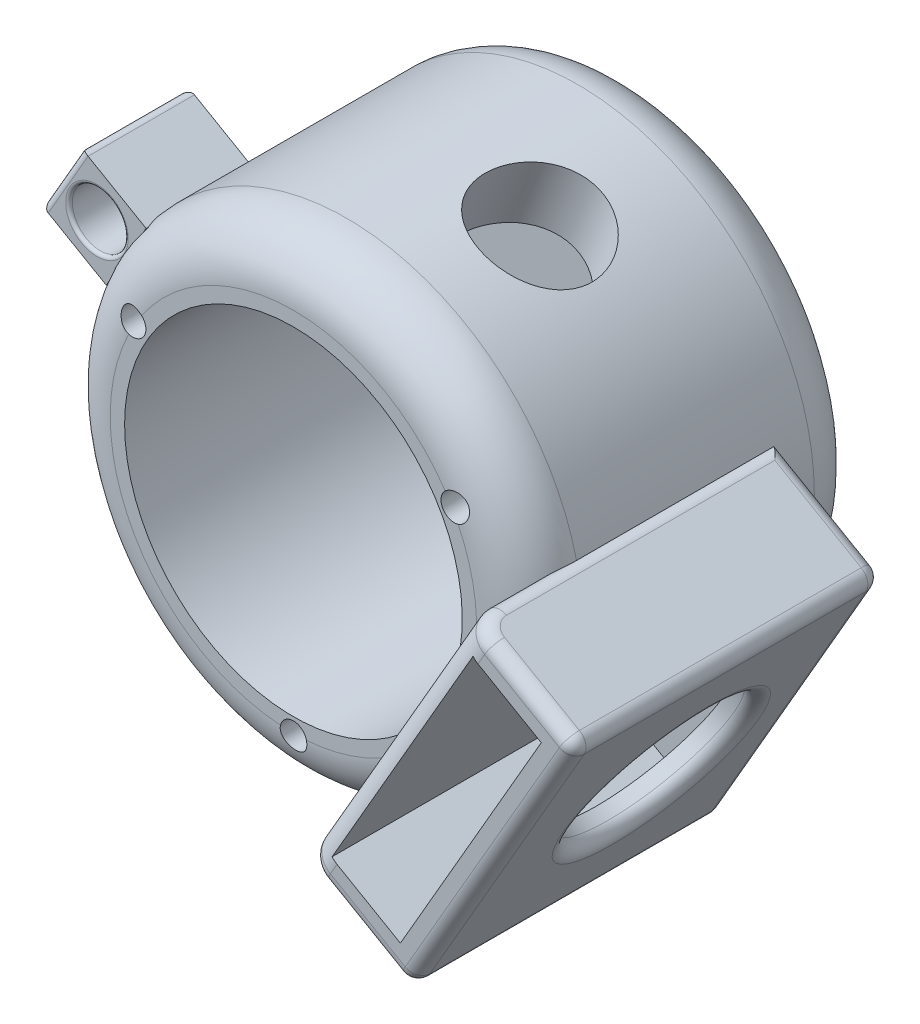
SolidWorks part; units mm, degrees
note: '?' marks a value the reader was unsure of.
material "Polyetheretherketone (PEEK)"
ref_plane "Front Plane" through (0, 0, 0) normal (0, 0, 1) x (1, 0, 0)
ref_plane "Top Plane" through (0, 0, 0) normal (0, 1, 0) x (1, 0, 0)
ref_plane "Right Plane" through (0, 0, 0) normal (1, 0, 0) x (0, 0, -1)
sketch "Sketch3" plane through (0, 0, 0) normal (0, 0, 1) x (1, 0, 0)
  line L1 (0, 0) -> (7.699, 4.445) construction
  line L4 (0, 0) -> (0, -6.985) construction
  line L5 (0, 0) -> (-6.0492, 3.4925) construction
  line L6 (0, 0) -> (6.0492, 3.4925) construction
  line L7 (0, -6.985) -> (-6.0492, 3.4925) construction
  line L8 (-6.0492, 3.4925) -> (6.0492, 3.4925) construction
  line L18 (6.0492, 3.4925) -> (0, -6.985) construction
  circle A0 centre (0, 0) radius 6.35
  circle A1 centre (-6.0492, 3.4925) radius 0.5
  circle A2 centre (0, -6.985) radius 0.5
  circle A3 centre (6.0492, 3.4925) radius 0.5
  circle A4 centre (0, 0) radius 8.89
  dimension "D1" = 12.7
  dimension "D5" = 120
  dimension "D7" = 1
  dimension "D3" = 17.78
  dimension "D2" = 6.985
  dimension "D4" = 120
extrude "Boss-Extrude2" add sketch "Sketch3" along normal blind 12.7
ref_plane "Plane2" through (-8.89, 0, 0) normal (-1, 0, 0) x (0, 0, 1)
fillet "Fillet5" radius 2 2 edges at (8.89, 0, 0) (8.89, 0, 12.7)
hole_wizard "#8 Clearance Hole1" positions "3DSketch1" profile "Sketch14" hole size "#8" standard "Ansi Inch"
sketch3d "3DSketch1"
  point P14 (3.179, 8.3022, 6.5635)
sketch "Sketch14" plane through (3.179, 8.3022, 6.5635) normal (0, 0, 1) x (-0.9339, 0.3576, 0)
  line L0 (0, 0) -> (0, 11.1994)
  line L1 (0, 11.1994) -> (2.1526, 9.906)
  line L2 (2.1526, 9.906) -> (2.1526, 0)
  line L5 (2.1526, 0) -> (0, 0)
  line L10 (0, 11.1994) -> (-2.1527, 9.906) construction
  line L11 (0, -6.35) -> (0, 107.95) construction
  dimension "Hole Dia." = 4.3053
  dimension "Hole Depth" = 9.906
  dimension "Drill Angle" = 118
ref_plane "Plane3" through (2.5916, -1.4963, 0) normal (0.866, -0.5, 0) x (0, 0, -1)
ref_plane "Plane4" through (7.699, -4.445, 0) normal (0.866, -0.5, 0) x (0, 0, -1)
sketch "Sketch15" plane through (7.699, -4.445, 0) normal (0.866, -0.5, 0) x (0, 0, -1)
  line L0 (-12.7, 5.7084) -> (-12.7, -5.7084) construction
  line L1 (-9.525, 0) -> (0, 0) construction
  line L2 (-14.775, 6.3) -> (-3.175, 6.3)
  line L3 (-14.775, 6.3) -> (-14.775, -6.3)
  line L4 (-14.775, -6.3) -> (-3.175, -6.3)
  line L5 (-3.175, 6.3) -> (-3.175, -6.3)
  line L6 (-9.525, 0) -> (-14.775, 0) construction
  dimension "D1" = 12.6
  dimension "D2" = 6.35
  dimension "D3" = 11.6
  dimension "D4" = 3.175
extrude "Boss-Extrude3" add sketch "Sketch15" against normal blind 2.54 and the other way blind 2.21
sketch "Sketch16" plane through (0, 0, 14.775) normal (0, 0, -1) x (-1, 0, 0)
  line L0 (0, 0) -> (-6.1488, -3.55) construction
  line L1 (-8.6493, 2.281) -> (-12.7629, -0.094) construction
  line L2 (-8.7988, 1.0399) -> (-3.4988, -8.1399)
  line L3 (-3.4988, -8.1399) -> (-6.0969, -9.6399)
  line L4 (-6.0969, -9.6399) -> (-11.3969, -0.4601)
  line L5 (-11.3969, -0.4601) -> (-8.7988, 1.0399)
  dimension "D1" = 7.1
  dimension "D2" = 10.6
  dimension "D3" = 3
extrude "Cut-Extrude6" cut sketch "Sketch16" along normal blind 10.6
sketch "Sketch17" plane through (8.7469, -5.05, 0) normal (-0.866, 0.5, 0) x (0, 0, 1)
  line L0 (8.475, 0) -> (3.175, 0) construction
  line L1 (3.175, -6.3) -> (3.175, 6.3) construction
  circle A0 centre (8.475, 0) radius 3.175
  dimension "D1" = 6.35
  dimension "D2" = 5.3
extrude "Cut-Extrude7" cut sketch "Sketch17" against normal through all
fillet "Fillet7" radius 1 1 edges at (5.4993, -3.175, 14.775)
fillet "Fillet6" radius 0.5 13 edges at (4.4061, -9.8185, 3.175) (2.3493, -8.631, 8.475) (4.8391, -10.0685, 14.775) (9.6129, -5.55, 3.175) (6.4629, -11.006, 8.975) (9.6129, -5.55, 14.775) (11.2004, -2.8004, 8.475) (12.7629, -0.094, 8.975) (11.1391, 0.8435, 14.775) (8.6493, 2.281, 8.475) (10.7061, 1.0935, 3.175) (8.9029, 2.1345, 14.4821) (2.6029, -8.7774, 14.4821)
ref_plane "Plane5" through (-7.699, 4.445, 0) normal (-0.866, 0.5, 0) x (0, 0, 1)
sketch "Sketch18" plane through (-7.699, 4.445, 0) normal (-0.866, 0.5, 0) x (0, 0, 1)
  line L0 (6.35, 0) -> (12.7, 0) construction
  line L2 (12.7, -0.4872) -> (12.7, 0.4872) construction
  line L4 (9.525, 1.5) -> (9.525, 0) construction
  line L5 (7.525, 1.5) -> (11.525, 1.5)
  line L6 (7.525, 1.5) -> (7.525, -1.5)
  line L7 (7.525, -1.5) -> (11.525, -1.5)
  line L8 (11.525, 1.5) -> (11.525, -1.5)
  line L9 (9.525, 0) -> (9.525, -1.5) construction
  dimension "D1" = 3
  dimension "D2" = 4
  dimension "D3" = 6.35
extrude "Boss-Extrude4" add sketch "Sketch18" along normal blind 2.5 and the other way blind 0.27
fillet "Fillet8" radius 0.25 4 edges at (-9.114, 6.994, 9.525) (-9.864, 5.695, 11.525) (-10.614, 4.396, 9.525) (-9.864, 5.695, 7.525)
sketch "Sketch19" plane through (0, 0, 11.525) normal (0, 0, 1) x (1, 0, 0)
  line L0 (0, 0) -> (-8.565, 4.945) construction
  line L1 (6.2799, -10.3229) -> (12.0799, -0.2771) construction
  line L2 (-10.489, 4.6125) -> (-9.239, 6.7775) construction
  circle A0 centre (-8.565, 4.945) radius 1.05
  point P6 (-7.5447, -4.356)
  dimension "D1" = 2.1
  dimension "D2" = 1.5
extrude "Cut-Extrude8" cut sketch "Sketch19" against normal blind 3.286
fillet "Fillet9" radius 0.125 1 edges at (-7.515, 4.945, 11.525)
ref_axis "Axis2" through (1.5675, 4.0936, 6.5635) along (0.3576, 0.9339, 0)?
ref_plane "Plane6" through (0, 0, 6.5635) normal (0, 0, -1) x (-1, 0, 0)
ref_plane "Plane7" through (0, 0, 1.801) normal (0, 0, -1) x (-1, 0, 0)
sketch "Sketch22" plane through (0, 0, 1.801) normal (0, 0, -1) x (-1, 0, 0)
  circle A0 centre (0, 0) radius 6.35
  circle A1 centre (0, 0) radius 6.35 construction
extrude "Boss-Extrude5" add sketch "Sketch22" along normal through all
